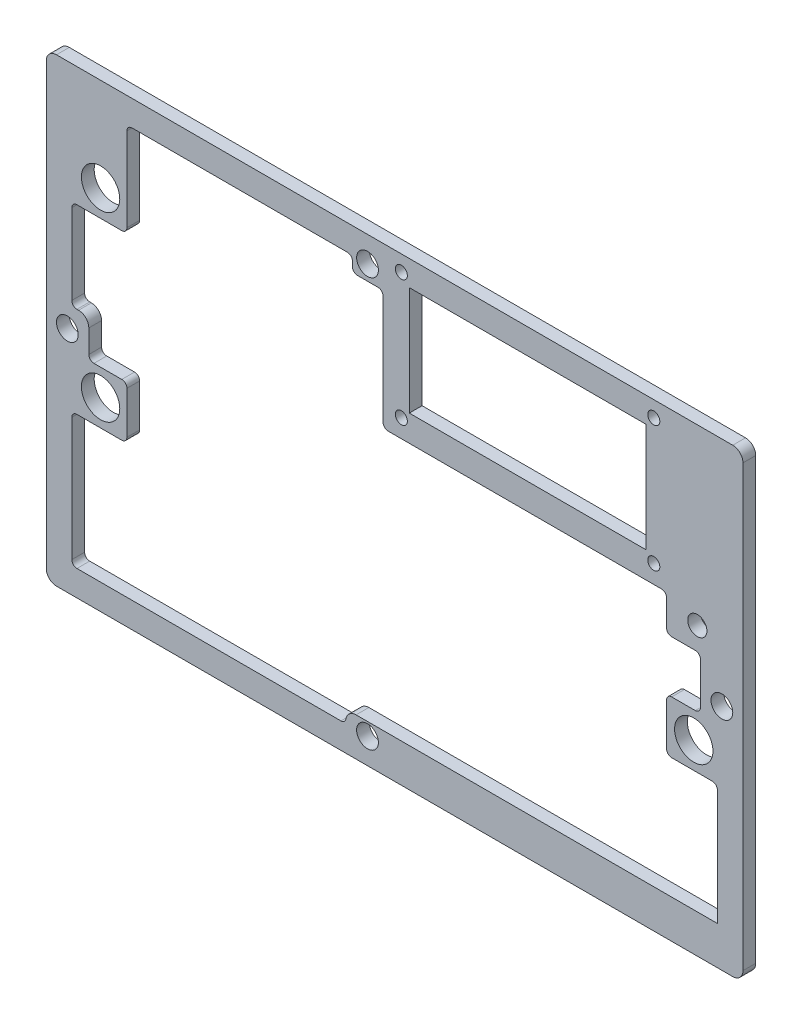
SolidWorks part; units mm, degrees
material "ABS PC"
ref_plane "Front Plane" through (0, 0, 0) normal (0, 0, 1) x (1, 0, 0)
ref_plane "Top Plane" through (0, 0, 0) normal (0, 1, 0) x (1, 0, 0)
ref_plane "Right Plane" through (0, 0, 0) normal (1, 0, 0) x (0, 0, -1)
sketch "Sketch1" plane through (0, 0, 0) normal (0, 0, 1) x (1, 0, 0)
  line L0 (94.968, 16.637) -> (-44.732, 16.637) construction
  line L1 (-61.4007, -97.663) -> (111.6368, -97.663)
  line L2 (-61.4007, -97.663) -> (-61.4007, 16.637)
  line L3 (-61.4007, 16.637) -> (111.6368, 16.637)
  line L4 (111.6368, -97.663) -> (111.6368, 16.637)
  line L5 (-61.4007, -97.663) -> (111.6368, 16.637) construction
  line L6 (-61.4007, 16.637) -> (111.6368, -97.663) construction
  point P4 (25.118, -40.513)
extrude "Boss-Extrude1" add sketch "Sketch1" along normal blind 3.175
sketch "Sketch3" plane through (0, 0, 3.175) normal (0, 0, 1) x (1, 0, 0)
  circle A0 centre (100.302, -26.543) radius 2.3813
  circle A1 centre (99.413, -51.6255) radius 4.7625
  circle A2 centre (-47.907, -51.6255) radius 4.7625
  circle A3 centre (-47.907, -6.5405) radius 4.7625
  dimension "D1" = 4.7625
  dimension "D2" = 9.525
extrude "Cut-Extrude1" cut sketch "Sketch3" against normal through all
hole_wizard "#6 Clearance Hole1" positions "Sketch5" profile "Sketch4" hole size "#6" standard "ANSI Inch" end condition through all
sketch "Sketch5" plane through (0, 0, 3.175) normal (0, 0, 1) x (1, 0, 0)
  point P0 (18.387, 10.287)
  point P3 (-56.162, -40.894)
  point P6 (106.398, -40.894)
  point P9 (18.387, -91.313)
sketch "Sketch4" plane through (18.387, 10.287, 3.175) normal (1, 0, 0) x (0, -1, 0)
  line L0 (0, 0) -> (0, 3.175)
  line L1 (0, 3.175) -> (2.1526, 3.175)
  line L2 (2.1526, 3.175) -> (2.1526, 0)
  line L5 (2.1526, 0) -> (0, 0)
  line L11 (0, -6.35) -> (0, 107.95) construction
  dimension "Thru Hole Dia." = 4.3053
  dimension "Thru Hole Depth" = 3.175
hole_wizard "#2 Clearance Hole1" positions "Sketch7" profile "Sketch6" hole size "#2" standard "ANSI Inch" end condition through all
sketch "Sketch7" plane through (0, 0, 3.175) normal (0, 0, 1) x (1, 0, 0)
  point P0 (26.788, 12.7)
  point P3 (89.488, 12.7)
  point P6 (89.488, -18.6)
  point P9 (26.788, -18.6)
sketch "Sketch6" plane through (26.788, 12.7, 3.175) normal (1, 0, 0) x (0, -1, 0)
  line L0 (0, 0) -> (0, 3.175)
  line L1 (0, 3.175) -> (1.3525, 3.175)
  line L2 (1.3525, 3.175) -> (1.3525, 0)
  line L5 (1.3525, 0) -> (0, 0)
  line L11 (0, -6.35) -> (0, 107.95) construction
  dimension "Thru Hole Dia." = 2.7051
  dimension "Thru Hole Depth" = 3.175
sketch "Sketch8" plane through (0, 0, 3.175) normal (0, 0, 1) x (1, 0, 0)
  line L9 (92.658, -23.1276) -> (22.2605, -23.1276)
  line L10 (22.2605, -23.1276) -> (22.2605, 6.5468)
  line L11 (22.2605, 6.5468) -> (14.6469, 6.5468)
  line L12 (92.658, -23.1276) -> (92.658, -32.1509)
  line L13 (28.768, 10.37) -> (28.768, -16.62)
  line L14 (28.768, -16.62) -> (87.508, -16.62)
  line L15 (87.508, -16.62) -> (87.508, 10.37)
  line L16 (87.508, 10.37) -> (28.768, 10.37)
  line L17 (28.768, 10.37) -> (28.768, -16.62)
  line L18 (28.768, -16.62) -> (87.508, -16.62)
  line L19 (87.508, -16.62) -> (87.508, 10.37)
  line L20 (87.508, 10.37) -> (28.768, 10.37)
  line L21 (92.658, -32.1509) -> (101.0704, -32.1509)
  line L22 (101.0704, -32.1509) -> (101.0704, -45.0855)
  line L23 (101.0704, -45.0855) -> (92.658, -45.0855)
  line L24 (92.658, -45.0855) -> (92.658, -58.1655)
  line L25 (92.658, -58.1655) -> (105.2868, -58.1655)
  line L26 (105.2868, -58.1655) -> (105.2868, -88.138)
  line L27 (105.2868, -88.138) -> (13.0594, -88.138)
  line L28 (13.0594, -88.138) -> (13.0594, -91.313)
  line L29 (13.0594, -91.313) -> (-55.0507, -91.313)
  line L30 (-55.0507, -91.313) -> (-55.0507, -58.1655)
  line L31 (-55.0507, -58.1655) -> (-41.367, -58.1655)
  line L32 (-41.367, -58.1655) -> (-41.367, -45.0855)
  line L33 (-41.367, -45.0855) -> (-50.8343, -45.0855)
  line L34 (-50.8343, -45.0855) -> (-50.8343, -35.5664)
  line L35 (-50.8343, -35.5664) -> (-55.0507, -35.5664)
  line L36 (-55.0507, -35.5664) -> (-55.0507, -13.0805)
  line L37 (-55.0507, -13.0805) -> (-41.367, -13.0805)
  line L38 (-41.367, -13.0805) -> (-41.367, 10.287)
  line L39 (14.6469, 6.5468) -> (14.6469, 10.287)
  line L40 (14.6469, 10.287) -> (-41.367, 10.287)
  line L43 (92.658, -45.0855) -> (109.0968, -45.0855) construction
  line L44 (111.6368, -97.663) -> (111.6368, 16.637) construction
  line L45 (-61.4007, -97.663) -> (111.6368, -97.663) construction
  line L46 (-61.4007, 16.637) -> (-61.4007, -97.663) construction
  line L47 (111.6368, 16.637) -> (-61.4007, 16.637) construction
  circle A1 centre (106.398, -40.894) radius 2.1526 construction
  circle A3 centre (18.387, -91.313) radius 2.1526 construction
  circle A8 centre (-56.162, -40.894) radius 2.1526 construction
  circle A11 centre (18.387, 10.287) radius 2.1526 construction
  circle A13 centre (26.788, -18.6) radius 1.3525 construction
  dimension "D1" = 1.27
  dimension "D10" = 1.5875
  dimension "D2" = 3.175
  dimension "D3" = 6.35
  dimension "D4" = 9.525
  dimension "D5" = 3.175
  dimension "D6" = 6.35
  dimension "D7" = 6.35
  dimension "D8" = 3.175
  dimension "D9" = 3.175
  dimension "D11" = 1.5875
  dimension "D12" = 6.35
  dimension "D13" = 3.175
  dimension "D14" = 3.175
extrude "Cut-Extrude2" cut sketch "Sketch8" against normal through all contours L19 L20 L17 L18 | L39 L40 L38 L37 L36 L35 L34 L33 L32 L31 L30 L29 L28 L27 L26 L25 L24 L23 L22 L21 L12 L9 L10 L11 region at (16.8246, -47.9652, 3.175) region at (58.138, -3.125, 3.175)
hole_wizard "#3 (0.213) Diameter Hole1" positions "3DSketch1" profile "Sketch9" hole size "#3" standard "ANSI Inch" end condition through all
sketch3d "3DSketch1"
  line L0 (18.387, 10.287, 0) -> (18.387, 10.287, 3.175) construction
  line L1 (-56.162, -40.894, 0) -> (-56.162, -40.894, 3.175) construction
  line L2 (18.387, -91.313, 0) -> (18.387, -91.313, 3.175) construction
  line L3 (106.398, -40.894, 0) -> (106.398, -40.894, 3.175) construction
  point P0 (18.387, 10.287, 3.175)
  point P5 (-56.162, -40.894, 3.175)
  point P9 (18.387, -91.313, 3.175)
  point P13 (106.398, -40.894, 3.175)
sketch "Sketch9" plane through (18.387, 10.287, 3.175) normal (1, 0, 0) x (0, -1, 0)
  line L0 (0, 0) -> (0, 3.175)
  line L1 (0, 3.175) -> (2.7051, 3.175)
  line L2 (2.7051, 3.175) -> (2.7051, 0)
  line L5 (2.7051, 0) -> (0, 0)
  line L11 (0, -6.35) -> (0, 107.95) construction
  dimension "Thru Hole Dia." = 5.4102
  dimension "Thru Hole Depth" = 3.175
hole_wizard "Ø3.0 (3) Diameter Hole1" positions "Sketch11" profile "Sketch10" hole size "Ø3.0" standard "ANSI Metric" end condition through all
sketch "Sketch11" plane through (0, 0, 3.175) normal (0, 0, 1) x (1, 0, 0)
  point P0 (26.788, 12.7)
  point P3 (89.488, 12.7)
  point P6 (89.488, -18.6)
  point P9 (26.788, -18.6)
sketch "Sketch10" plane through (26.788, 12.7, 3.175) normal (1, 0, 0) x (0, -1, 0)
  line L0 (0, 0) -> (0, 3.175)
  line L1 (0, 3.175) -> (1.5, 3.175)
  line L2 (1.5, 3.175) -> (1.5, 0)
  line L5 (1.5, 0) -> (0, 0)
  line L11 (0, -6.35) -> (0, 107.95) construction
  dimension "Thru Hole Dia." = 3
  dimension "Thru Hole Depth" = 3.175
fillet "Fillet1" radius 1.27 21 edges at (-41.367, 10.287, 1.5875) (-41.367, -13.0805, 1.5875) (-55.0507, -13.0805, 1.5875) (-55.0507, -35.5664, 1.5875) (-50.8343, -45.0855, 1.5875) (-41.367, -45.0855, 1.5875) (-41.367, -58.1655, 1.5875) (-55.0507, -58.1655, 1.5875) (-55.0507, -91.313, 1.5875) (13.0594, -91.313, 1.5875) (105.2868, -58.1655, 1.5875) (92.658, -58.1655, 1.5875) (92.658, -45.0855, 1.5875) (101.0704, -45.0855, 1.5875) (101.0704, -32.1509, 1.5875) (92.658, -32.1509, 1.5875) (92.658, -23.1276, 1.5875) (22.2605, -23.1276, 1.5875) (14.6469, 6.5468, 1.5875) (22.2605, 6.5468, 1.5875) (14.6469, 10.287, 1.5875)
fillet "Fillet2" radius 2.54 6 edges at (13.0594, -88.138, 1.5875) (-50.8343, -35.5664, 1.5875) (111.6368, 16.637, 1.5875) (111.6368, -97.663, 1.5875) (-61.4007, -97.663, 1.5875) (-61.4007, 16.637, 1.5875)
